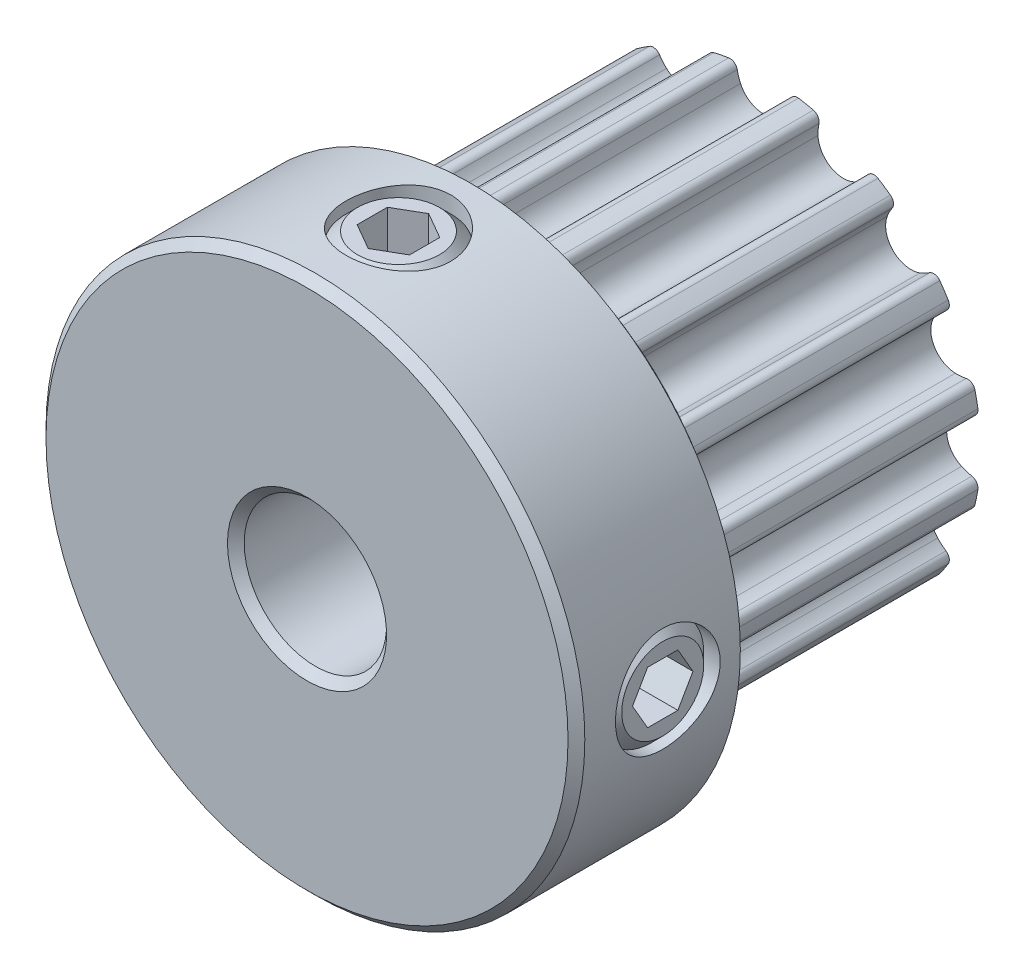
SolidWorks part; units mm, degrees
ref_plane "Front Plane" through (0, 0, 0) normal (0, 0, 1) x (1, 0, 0)
ref_plane "Top Plane" through (0, 0, 0) normal (0, 1, 0) x (1, 0, 0)
ref_plane "Right Plane" through (0, 0, 0) normal (1, 0, 0) x (0, 0, -1)
sketch "Sketch1" plane through (0, 0, 0) normal (0, 0, 1) x (1, 0, 0)
  line L1 (-2.553, 6.1245) -> (2.553, 6.1245) construction
  line L4 (0, 0) -> (0, 6.1245) construction
  line L5 (0, 6.1245) -> (0, 12.0668) construction
  line L6 (0, 7.6455) -> (2.9417, 7.0569) construction
  line L7 (2.9417, 7.0569) -> (3.8741, 6.6682) construction
  line L8 (2.9417, 7.0569) -> (2.553, 6.1245) construction
  line L9 (-2.9417, 7.0569) -> (-2.553, 6.1245) construction
  line L10 (-2.7951, 6.7052) -> (-3.7579, 9.015)
  line L11 (-3.7579, 9.015) -> (3.7579, 9.015)
  line L12 (3.7579, 9.015) -> (2.7951, 6.7052)
  circle A0 centre (0, 0) radius 7.6455 construction
  circle A1 centre (0, 0) radius 9.015 construction
  circle A2 centre (0, 0) radius 7.2645 construction
  arc A3 (-0.7739, 6.6229) -> (0.7739, 6.6229) centre (0, 6.9745) ccw
  arc A4 (-0.7739, 6.6229) -> (-0.8836, 6.9694) centre (0.61, 7.2516) cw
  arc A5 (-2.7951, 6.7052) -> (-1.1695, 7.1697) centre (0, 0) cw
  arc A6 (-0.8836, 6.9694) -> (-1.1695, 7.1697) centre (-1.1292, 6.923) ccw
  arc A7 (2.7951, 6.7052) -> (1.1695, 7.1697) centre (0, 0) ccw
  arc A8 (0.8836, 6.9694) -> (1.1695, 7.1697) centre (1.1292, 6.923) cw
  arc A9 (0.7739, 6.6229) -> (0.8836, 6.9694) centre (-0.61, 7.2516) ccw
  point P6 (0, 20.9083)
  point P11 (0, 7.6455)
  point P13 (0, 9.015)
  point P14 (0, 7.2645)
  dimension "D1" = 8.8416
  dimension "D2" = 4.4213
sketch "Sketch2" plane through (0, 0, 0) normal (1, 0, 0) x (0, 0, -1)
  line L0 (-8.775, 2.3812) -> (8.775, 2.3812)
  line L1 (-8.775, 2.3812) -> (-8.775, 9.015)
  line L2 (-3.29, 9.015) -> (-8.775, 9.015)
  line L3 (-3.925, 2.3813) -> (-3.925, 9.015) construction
  line L4 (-3.925, 9.015) -> (-2.655, 9.015) construction
  line L5 (-2.655, 9.015) -> (-2.655, 7.2645) construction
  line L6 (-2.655, 7.2645) -> (7.505, 7.2645)
  line L7 (7.505, 7.2645) -> (7.505, 9.015) construction
  line L8 (7.505, 9.015) -> (8.775, 9.015) construction
  line L9 (8.775, 9.015) -> (8.775, 2.3812)
  line L10 (-8.775, 0) -> (8.775, 0) construction
  line L11 (8.14, 9.015) -> (7.505, 8.1398)
  line L12 (-2.655, 8.1398) -> (-3.29, 9.015)
  line L14 (-2.655, 8.1398) -> (-2.655, 7.2645)
  line L15 (7.505, 7.2645) -> (7.505, 8.1398)
  line L16 (8.14, 9.015) -> (8.775, 9.015)
  arc A0 (-2.655, 8.1398) -> (-3.29, 9.015) centre (-3.5757, 8.1398) ccw construction
  arc A1 (7.505, 8.1398) -> (8.14, 9.015) centre (8.4257, 8.1398) cw construction
  point P12 (-2.655, 8.1398)
  point P14 (-3.29, 9.015)
  point P20 (7.505, 8.1398)
  point P21 (8.14, 9.015)
  point P25 (7.505, 0)
  point P26 (-2.655, 0)
  dimension "OA" = 17.55
  dimension "Bore" = 4.7625
  dimension "Outside Width" = 11.43
  dimension "Inside Width" = 10.16
revolve "Revolve1" add sketch "Sketch2" angle 360 mid plane about L10
sketch "Sketch3" plane through (0, 0, 0) normal (0, 0, 1) x (1, 0, 0)
  line L6 (3.7579, 9.015) -> (-3.7579, 9.015)
  line L7 (2.7951, 6.7052) -> (3.7579, 9.015)
  line L8 (-3.7579, 9.015) -> (-2.7951, 6.7052)
  line L9 (3.7579, 9.015) -> (-3.7579, 9.015)
  line L10 (2.7951, 6.7052) -> (3.7579, 9.015)
  line L11 (-3.7579, 9.015) -> (-2.7951, 6.7052)
  arc A8 (2.7951, 6.7052) -> (1.1695, 7.1697) centre (0, 0) ccw
  arc A9 (1.1695, 7.1697) -> (0.8836, 6.9694) centre (1.1292, 6.923) ccw
  arc A10 (0.7739, 6.6229) -> (0.8836, 6.9694) centre (-0.61, 7.2516) ccw
  arc A11 (-0.7739, 6.6229) -> (0.7739, 6.6229) centre (0, 6.9745) ccw
  arc A12 (-0.8836, 6.9694) -> (-0.7739, 6.6229) centre (0.61, 7.2516) ccw
  arc A13 (-0.8836, 6.9694) -> (-1.1695, 7.1697) centre (-1.1292, 6.923) ccw
  arc A14 (-1.1695, 7.1697) -> (-2.7951, 6.7052) centre (0, 0) ccw
  arc A15 (2.7951, 6.7052) -> (1.1695, 7.1697) centre (0, 0) ccw
  arc A16 (1.1695, 7.1697) -> (0.8836, 6.9694) centre (1.1292, 6.923) ccw
  arc A17 (0.7739, 6.6229) -> (0.8836, 6.9694) centre (-0.61, 7.2516) ccw
  arc A18 (-0.7739, 6.6229) -> (0.7739, 6.6229) centre (0, 6.9745) ccw
  arc A19 (-0.8836, 6.9694) -> (-0.7739, 6.6229) centre (0.61, 7.2516) ccw
  arc A20 (-0.8836, 6.9694) -> (-1.1695, 7.1697) centre (-1.1292, 6.923) ccw
  arc A21 (-1.1695, 7.1697) -> (-2.7951, 6.7052) centre (0, 0) ccw
  dimension "D1" = 0
extrude "Cut-Extrude1" cut sketch "Sketch3" against normal up to vertex (7.505 mm away) from vertex up to point (0, 7.2645, -7.505) starting at point (0, 7.2645, 2.655)
pattern_circular "CirPattern1" count 16 over 360 about axis through (0, 0, 8.775) along (0, 0, 1) of "Cut-Extrude1"
sketch "Sketch4" plane through (0, 0, 0) normal (1, 0, 0) x (0, -1, 0)
  line L0 (0, -2.655) -> (0, -8.775) construction
  line L1 (-2.3812, -8.775) -> (2.3812, -8.775) construction
  line L2 (8.1398, -2.655) -> (-8.1398, -2.655) construction
  circle A0 centre (0, -5.715) radius 1.7526
extrude "Cut-Extrude2" cut sketch "Sketch4" along normal through all
ref_plane "Plane1" through (0, 0, 5.715) normal (0, 0, 1) x (1, 0, 0)
sketch "Sketch5" plane through (0, 0, 5.715) normal (0, 0, 1) x (1, 0, 0)
  line L0 (0, 0) -> (0, 9.015) construction
  line L1 (2.3812, -1.3716) -> (2.3812, 0)
  line L2 (2.7622, -1.7526) -> (8.462, -1.7526)
  line L3 (2.3812, 0) -> (9.015, 0) construction
  line L4 (2.3812, 0) -> (8.843, 0)
  line L5 (8.843, 0) -> (8.843, -1.3716)
  line L6 (2.7622, -1.7526) -> (2.3812, -1.3716)
  line L7 (8.843, -1.3716) -> (8.462, -1.7526)
  circle A0 centre (0, 0) radius 9.015 construction
  circle A1 centre (0, 0) radius 2.3812 construction
  point P2 (2.3812, -1.7526)
  point P11 (8.843, -1.7526)
revolve "Revolve2" add sketch "Sketch5" angle 360 mid plane about L4
sketch "Sketch6" plane through (8.843, 5.3841, 0) normal (-1, 0, 0) x (0, -1, 0)
  line L1 (5.3841, 6.7269) -> (4.5078, 6.2209)
  line L2 (4.5078, 6.2209) -> (4.5078, 5.2091)
  line L3 (4.5078, 5.2091) -> (5.3841, 4.7031)
  line L4 (5.3841, 4.7031) -> (6.2604, 5.2091)
  line L5 (6.2604, 5.2091) -> (6.2604, 6.2209)
  line L6 (6.2604, 6.2209) -> (5.3841, 6.7269)
  circle A0 centre (5.3841, 5.715) radius 0.8763 construction
  dimension "D1" = 1.7526
extrude "Cut-Extrude3" cut sketch "Sketch6" along normal blind 1.3144
pattern_circular "CirPattern3" count 2 over 90 about axis through (0, 0, 8.775) along (0, 0, 1) of "Cut-Extrude2", "Revolve2", "Cut-Extrude3"
chamfer "Chamfer1" distance 0.2807 angle 45 2 edges at (2.3812, 0, 8.775) (9.015, 0, 8.775)
ref_axis "Center Axis 1" through (0, 0, -8.775) along (0, 0, 1)
ref_plane "Contact Plane 1" through (0, 0, 8.775) normal (0, 0, 1) x (1, 0, 0)
ref_plane "Contact Plane 2" through (0, 0, -8.775) normal (0, 0, -1) x (-1, 0, 0)
sketch "Sketch7" plane through (0, 0, 2.655) normal (0, 0, -1) x (-1, 0, 0)
  circle A0 centre (0, 0) radius 9.015 construction
  circle A1 centre (0, 0) radius 9.015
extrude "Cut-Extrude4" [suppressed] cut sketch "Sketch7" along normal through all from offset 7
sketch "Sketch8" plane through (0, 0, -8.775) normal (0, 0, -1) x (-1, 0, 0)
  circle A1 centre (0, 0) radius 9.015
  circle A2 centre (0, 0) radius 9.015
  dimension "D1" = 0
extrude "Cut-Extrude5" cut sketch "Sketch8" against normal offset from surface (2.27 mm away) 1 up to face at (0, 0, -7.505) offset beyond the face yes
equation "\"D2@Sketch1\"= \"D1@Sketch1\" / 2"
equation "\"D1@Sketch6\" = \"Set Screw@Sketch4\" / 2"
equation "\"D1@Cut-Extrude3\" = \"D1@Sketch6\"*.75"
